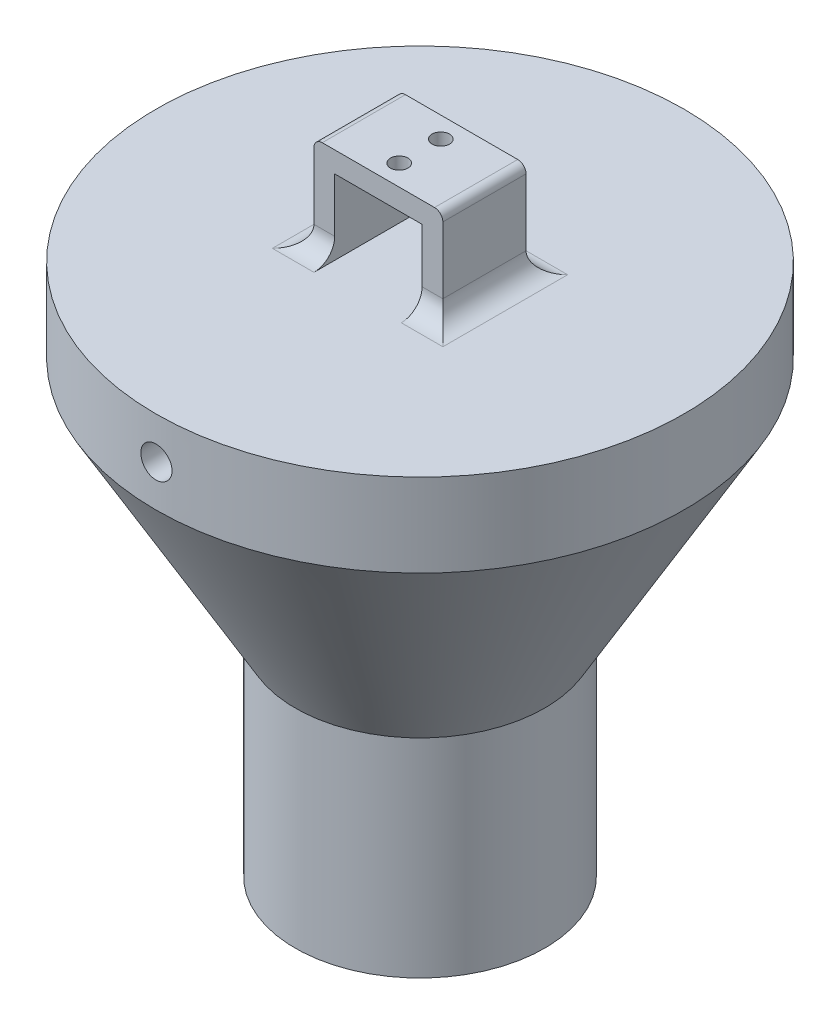
SolidWorks part; units mm, degrees
ref_plane "Front Plane" through (0, 0, 0) normal (0, 0, 1) x (1, 0, 0)
ref_plane "Top Plane" through (0, 0, 0) normal (0, 1, 0) x (1, 0, 0)
ref_plane "Right Plane" through (0, 0, 0) normal (1, 0, 0) x (0, 0, -1)
sketch "Sketch1" plane through (0, 0, 0) normal (0, 0, 1) x (1, 0, 0)
  line L0 (0, 0) -> (0, 88)
  line L1 (0, 0) -> (-30, 0)
  line L2 (-30, 0) -> (-30, 50)
  line L3 (-30, 50) -> (-63.4863, 108)
  line L5 (-63.4863, 108) -> (-63.4863, 128)
  line L6 (-63.4863, 128) -> (0, 128)
  line L7 (0, 128) -> (0, 88)
  line L8 (-30, 50) -> (0, 50)
  dimension "D1" = 88
  dimension "D2" = 30
  dimension "D3" = 50
  dimension "D4" = 150
  dimension "D5" = 20
  dimension "D6" = 63.4863
revolve "Revolve1" add sketch "Sketch1" angle 360 about L0 region at (-26.7225, 93.7976, 0)
shell "Shell1" thickness 10 removed face at (0, 50, -30)
sketch "Sketch4" plane through (0, 0, 0) normal (0, 0, 1) x (1, 0, 0)
  line L0 (0, 128) -> (0, 108) construction
  line L1 (63.4863, 128) -> (-63.4863, 128) construction
  line L2 (63.4863, 108) -> (-63.4863, 108) construction
  circle A0 centre (0, 118) radius 3.75
  dimension "D1" = 7.5
extrude "Cut-Extrude2" cut sketch "Sketch4" against normal mid plane 150
revolve "Revolve2" add sketch "Sketch1<3>" angle 360 about L0 region at (-15, 25, 0)
sketch "Sketch1<3>" plane through (0, 0, 0) normal (0, 0, 1) x (1, 0, 0) same geometry as "Sketch1"
shell "Shell3" thickness 12 removed face at (0, 0, -30) removed face at (0, 50, 18.453)
sketch "Sketch5" plane through (0, 0, 0) normal (0, -1, 0) x (1, 0, 0)
  circle A0 centre (0, 0) radius 20.5
  circle A1 centre (0, 0) radius 25.5
  dimension "D1" = 41
  dimension "D2" = 51
extrude "Cut-Extrude3" cut sketch "Sketch5" against normal blind 2.5
sketch "Sketch7" plane through (0, 0, 0) normal (0, 0, 1) x (1, 0, 0)
  line L0 (0, 128) -> (0, 143) construction
  line L1 (63.4863, 128) -> (-63.4863, 128) construction
  line L2 (7.5, 128) -> (10.5, 128)
  line L3 (-7.5, 128) -> (7.5, 128) construction
  line L4 (-7.5, 128) -> (-7.5, 143) construction
  line L5 (-7.5, 143) -> (7.5, 143) construction
  line L6 (7.5, 128) -> (7.5, 143) construction
  line L7 (-7.5, 128) -> (7.5, 143) construction
  line L8 (-7.5, 143) -> (7.5, 128) construction
  line L9 (10.5, 128) -> (10.5, 146)
  line L10 (10.5, 146) -> (-10.5, 146)
  line L11 (-10.5, 128) -> (-10.5, 146)
  line L12 (10.5, 128) -> (15.5, 128)
  line L13 (15.5, 128) -> (15.5, 151)
  line L14 (15.5, 151) -> (-15.5, 151)
  line L15 (-15.5, 128) -> (-15.5, 151)
  line L16 (-10.5, 128) -> (-15.5, 128)
  point P5 (0, 135.5)
  point P15 (0, 146)
  point P20 (0, 151)
  dimension "D1" = 15
  dimension "D2" = 15
  dimension "D3" = 3
  dimension "D4" = 3
  dimension "D5" = 5
  dimension "D6" = 5
extrude "Boss-Extrude1" add sketch "Sketch7" along normal mid plane 20 contours L16 L11 L10 L9 L12 L13 L14 L15 region at (10.886, 137, 0)
sketch "Sketch8" plane through (0, 151, 0) normal (0, 1, 0) x (1, 0, 0)
  line L0 (0, 10) -> (0, 0) construction
  line L1 (15.5, 10) -> (-15.5, 10) construction
  line L2 (0, 0) -> (0, -10) construction
  line L3 (-15.5, 0) -> (15.5, 0) construction
  line L4 (-15.5, -10) -> (-15.5, 10) construction
  line L5 (15.5, -10) -> (15.5, 10) construction
  line L6 (15.5, -10) -> (-15.5, -10) construction
  circle A0 centre (0, 5) radius 2.1
  circle A1 centre (0, -5) radius 2.1
  dimension "D1" = 4.2
extrude "Cut-Extrude4" cut sketch "Sketch8" against normal blind 10
fillet "Fillet1" radius 5 6 edges at (15.5, 128, 0) (-15.5, 128, 0) (13, 128, -10) (-13, 128, -10) (13, 128, 10) (-13, 128, 10)
fillet "Fillet2" radius 2 2 edges at (-15.5, 151, 0) (15.5, 151, 0)
